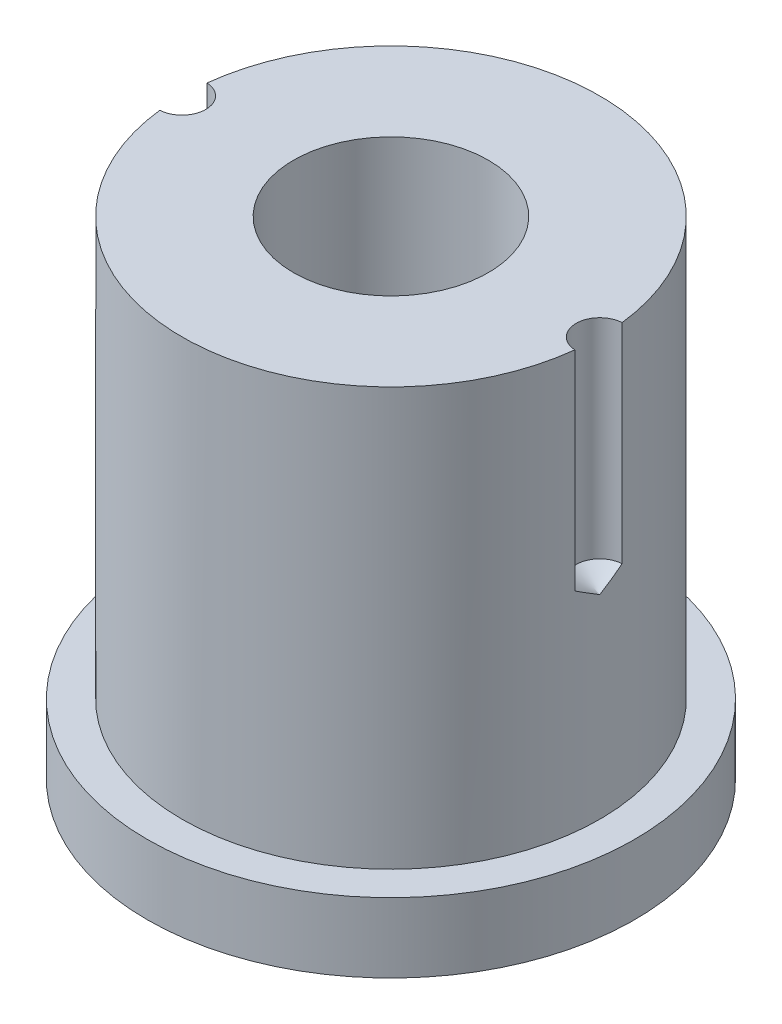
SolidWorks part; units mm, degrees
material "Commercial Bronze, UNS C22000 (90-10 Bronze)"
ref_plane "Front Plane" through (0, 0, 0) normal (0, 0, 1) x (1, 0, 0)
ref_plane "Top Plane" through (0, 0, 0) normal (0, 1, 0) x (1, 0, 0)
ref_plane "Right Plane" through (0, 0, 0) normal (1, 0, 0) x (0, 0, -1)
sketch "Sketch1" plane through (0, 0, 0) normal (0, 1, 0) x (1, 0, 0)
  circle A0 centre (0, 0) radius 35
  dimension "D1" = 70
extrude "Boss-Extrude1" add sketch "Sketch1" along normal blind 10
sketch "Sketch2" plane through (0, 10, 0) normal (0, 1, 0) x (1, 0, 0)
  circle A0 centre (0, 0) radius 30
  dimension "D1" = 60
extrude "Boss-Extrude2" add sketch "Sketch2" along normal blind 60
sketch "Sketch3" plane through (0, 70, 0) normal (0, 1, 0) x (1, 0, 0)
  circle A0 centre (0, 0) radius 14
  dimension "D1" = 28
extrude "Cut-Extrude1" cut sketch "Sketch3" against normal through all
hole_wizard "Ø8.0mm Dowel Hole1" positions "Sketch4" profile "Sketch5" hole size "Ø8.0" standard "ISO"
sketch "Sketch4" plane through (0, 70, 0) normal (0, 1, 0) x (1, 0, 0)
  circle A0 centre (0, 0) radius 30 construction
  circle A1 centre (0, 0) radius 30 construction
  point P0 (-30, 0)
  point P4 (30, 0)
sketch "Sketch5" plane through (-30, 70, 0) normal (1, 0, 0) x (0, 0, 1)
  line L0 (0, 0) -> (0, 32.0429)
  line L1 (0, 32.0429) -> (3.4, 30)
  line L2 (3.4, 30) -> (3.4, 0)
  line L5 (3.4, 0) -> (0, 0)
  line L10 (0, 32.0429) -> (-3.4, 30) construction
  line L11 (0, -6.35) -> (0, 107.95) construction
  dimension "Hole Dia." = 6.8
  dimension "Hole Depth" = 30
  dimension "Drill Angle" = 118
